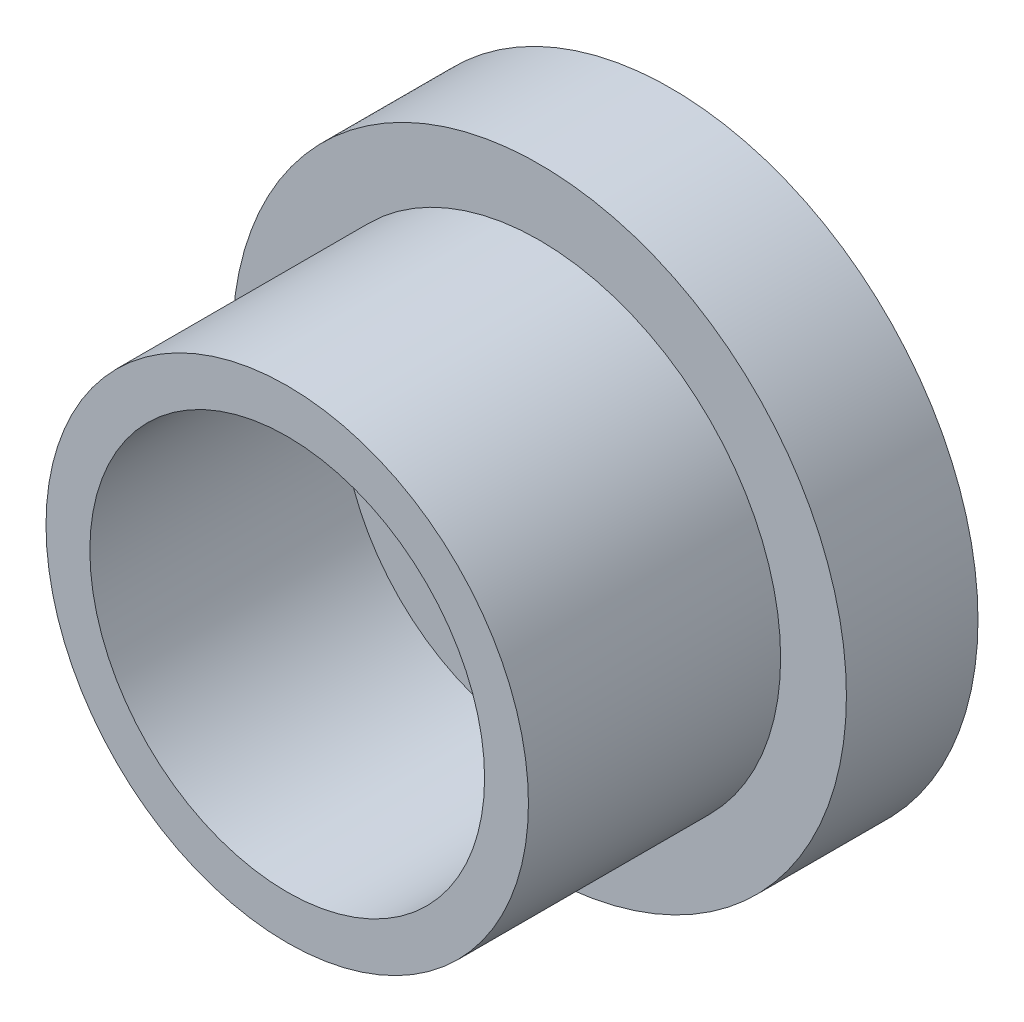
SolidWorks part; units mm, degrees
material "Латунь"
ref_plane "Спереди" through (0, 0, 0) normal (0, 0, 1) x (1, 0, 0)
ref_plane "Сверху" through (0, 0, 0) normal (0, 1, 0) x (1, 0, 0)
ref_plane "Справа" through (0, 0, 0) normal (1, 0, 0) x (0, 0, -1)
sketch "Эскиз1" plane through (0, 0, 0) normal (0, 0, 1) x (1, 0, 0)
  circle A0 centre (0, 0) radius 2.8
  circle A1 centre (0, 0) radius 1.8
  circle A2 centre (0, 0) radius 2.2
  dimension "D1" = 3.6
  dimension "D2" = 5.6
  dimension "D3" = 4.4
extrude "Бобышка-Вытянуть2" add sketch "Эскиз1" along normal blind 3.5 contours A2 A1 region at (-2.1378, 0, 0)
extrude "Бобышка-Вытянуть3" add sketch "Эскиз1<6>" along normal blind 1.2 contours A0
sketch "Эскиз1<6>" plane through (0, 0, 0) normal (0, 0, 1) x (1, 0, 0) same geometry as "Эскиз1"
